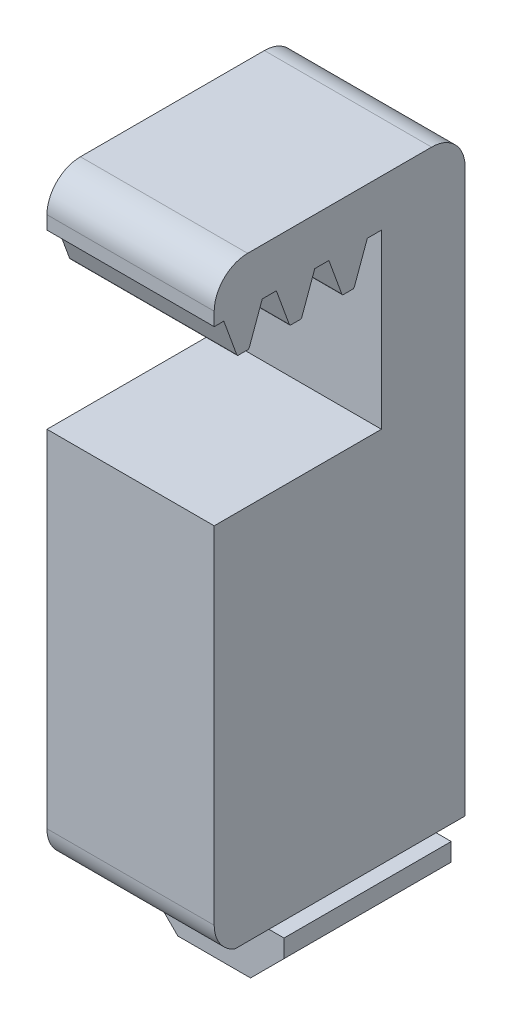
SolidWorks part; units mm, degrees
material "PLA Grey"
ref_plane "Front Plane" through (0, 0, 0) normal (0, 0, 1) x (1, 0, 0)
ref_plane "Top Plane" through (0, 0, 0) normal (0, 1, 0) x (1, 0, 0)
ref_plane "Right Plane" through (0, 0, 0) normal (1, 0, 0) x (0, 0, -1)
sketch "Sketch1" plane through (0, 0, 0) normal (1, 0, 0) x (0, 0, -1)
  line L0 (6.35, 0) -> (6.35, -6.096)
  line L1 (0, 45.466) -> (12.7, 45.466)
  line L2 (0, 45.466) -> (0, 39.116)
  line L3 (0, 39.116) -> (12.7, 39.116)
  line L5 (12.7, 45.466) -> (19.05, 45.466)
  line L6 (12.7, 39.116) -> (12.7, 29.21)
  line L7 (6.35, -6.096) -> (19.05, -6.096)
  line L8 (19.05, 45.466) -> (19.05, -6.096)
  line L9 (12.7, 29.21) -> (0, 29.21)
  line L11 (6.35, 0) -> (0, 0)
  line L12 (0, 29.21) -> (0, 0)
  line L13 (12.7, 29.21) -> (-1206.5, 29.21) construction
  dimension "D1" = 6.35
  dimension "D2" = 12.7
  dimension "D3" = 9.906
  dimension "D4" = 6.35
  dimension "D5" = 12.7
  dimension "D6" = 6.096
extrude "Boss-Extrude1" add sketch "Sketch1" along normal mid plane 12.7
sketch "Sketch2" plane through (6.35, 0, 0) normal (1, 0, 0) x (0, 0, -1)
  line L0 (3.6499, 41.91) -> (4.7203, 41.91) construction
  line L1 (5.6948, 39.2327) -> (4.7203, 41.91) construction
  line L2 (6.4261, 39.0652) -> (5.934, 39.0652) construction
  line L3 (7.6397, 41.91) -> (6.6653, 39.2327) construction
  line L4 (7.6397, 41.91) -> (8.7102, 41.91) construction
  line L5 (9.6846, 39.2327) -> (8.7102, 41.91) construction
  line L6 (10.4159, 39.0652) -> (9.9238, 39.0652) construction
  line L7 (11.6296, 41.91) -> (10.6551, 39.2327) construction
  line L8 (11.6296, 41.91) -> (12.7, 41.91) construction
  line L9 (3.6499, 41.91) -> (4.7203, 41.91)
  line L10 (5.6948, 39.2327) -> (4.7203, 41.91)
  line L11 (6.4261, 39.0652) -> (5.934, 39.0652)
  line L12 (7.6397, 41.91) -> (6.6653, 39.2327)
  line L13 (7.6397, 41.91) -> (8.7102, 41.91)
  line L14 (9.6846, 39.2327) -> (8.7102, 41.91)
  line L15 (10.4159, 39.0652) -> (9.9238, 39.0652)
  line L16 (11.6296, 41.91) -> (10.6551, 39.2327)
  line L17 (11.6296, 41.91) -> (12.7, 41.91)
  line L18 (12.7, 41.91) -> (12.7, 29.21)
  line L19 (12.7, 39.116) -> (12.7, 29.21) construction
  line L20 (12.7, 29.21) -> (3.6499, 29.21)
  line L21 (3.6499, 29.21) -> (3.6499, 41.91)
  line L22 (12.7, 29.21) -> (0, 29.21) construction
  arc A0 (5.6948, 39.2327) -> (5.934, 39.0652) centre (5.934, 39.3198) ccw construction
  arc A1 (6.4261, 39.0652) -> (6.6653, 39.2327) centre (6.4261, 39.3198) ccw construction
  arc A2 (9.6846, 39.2327) -> (9.9238, 39.0652) centre (9.9238, 39.3198) ccw construction
  arc A3 (10.4159, 39.0652) -> (10.6551, 39.2327) centre (10.4159, 39.3198) ccw construction
  arc A4 (5.6948, 39.2327) -> (5.934, 39.0652) centre (5.934, 39.3198) ccw
  arc A5 (6.4261, 39.0652) -> (6.6653, 39.2327) centre (6.4261, 39.3198) ccw
  arc A6 (9.6846, 39.2327) -> (9.9238, 39.0652) centre (9.9238, 39.3198) ccw
  arc A7 (10.4159, 39.0652) -> (10.6551, 39.2327) centre (10.4159, 39.3198) ccw
extrude "Cut-Extrude1" cut sketch "Sketch2" against normal through all
pattern_linear "LPattern1" count 10 spacing 3.9898 along (0, 0, 1) of "Cut-Extrude1"
sketch "Sketch3" plane through (0, 0, -19.05) normal (0, 0, -1) x (-1, 0, 0)
  line L0 (-6.35, -6.096) -> (-2.8393, -6.1)
  line L1 (2.8393, -6.1) -> (5.5, -3.4393) construction
  line L2 (5.5, -3.4393) -> (5.5, -1.8) construction
  line L3 (5.5, -1.8) -> (3.125, -1.8) construction
  line L4 (3.125, -1.8) -> (3.125, -1.455) construction
  line L5 (3.125, -1.455) -> (4.58, 0) construction
  line L6 (15.42, 0) -> (4.58, 0) construction
  line L7 (-4.58, 0) -> (-9.5, 0) construction
  line L8 (-3.125, -1.455) -> (-4.58, 0) construction
  line L9 (-3.125, -1.8) -> (-3.125, -1.455) construction
  line L10 (-5.5, -1.8) -> (-3.125, -1.8) construction
  line L11 (-5.5, -3.4393) -> (-5.5, -1.8) construction
  line L12 (-2.8393, -6.1) -> (-5.5, -3.4393) construction
  line L13 (2.8393, -6.1) -> (6.35, -6.096)
  line L15 (2.8393, -6.1) -> (5.5, -3.4393)
  line L16 (5.5, -3.4393) -> (5.5, -1.8)
  line L17 (5.5, -1.8) -> (3.125, -1.8)
  line L18 (3.125, -1.8) -> (3.125, -1.455)
  line L19 (3.125, -1.455) -> (4.58, 0)
  line L20 (15.42, 0) -> (4.58, 0)
  line L21 (-4.58, 0) -> (-9.5, 0)
  line L22 (-3.125, -1.455) -> (-4.58, 0)
  line L23 (-3.125, -1.8) -> (-3.125, -1.455)
  line L24 (-5.5, -1.8) -> (-3.125, -1.8)
  line L25 (-5.5, -3.4393) -> (-5.5, -1.8)
  line L26 (-2.8393, -6.1) -> (-5.5, -3.4393)
  line L29 (-9.5, 0) -> (-6.35, -6.096)
  line L32 (6.35, -6.096) -> (15.42, 0)
extrude "Cut-Extrude2" cut sketch "Sketch3" against normal through all
fillet "Fillet1" radius 2.54 3 edges at (0, 0, 0) (0, 45.466, 0) (0, 45.466, -19.05)
sketch "Sketch5" plane through (0, 0, -19.05) normal (0, 0, -1) x (-1, 0, 0)
  line L0 (6.35, 0) -> (4.58, 0) construction
  line L1 (4.58, 0) -> (3.125, -1.455) construction
  line L2 (3.125, -1.455) -> (3.125, -1.8) construction
  line L3 (3.125, -1.8) -> (5.5, -1.8) construction
  line L4 (5.5, -1.8) -> (5.5, -3.4393) construction
  line L5 (5.5, -3.4393) -> (2.8433, -6.096) construction
  line L6 (-2.8433, -6.096) -> (2.8433, -6.096) construction
  line L7 (-2.8433, -6.096) -> (-5.5, -3.4393) construction
  line L8 (-5.5, -3.4393) -> (-5.5, -1.8) construction
  line L9 (-5.5, -1.8) -> (-3.125, -1.8) construction
  line L10 (-3.125, -1.8) -> (-3.125, -1.455) construction
  line L11 (-3.125, -1.455) -> (-4.58, 0) construction
  line L12 (-4.58, 0) -> (-6.35, 0) construction
  line L13 (6.35, 0) -> (4.58, 0)
  line L14 (4.58, 0) -> (3.125, -1.455)
  line L15 (3.125, -1.455) -> (3.125, -1.8)
  line L16 (3.125, -1.8) -> (5.5, -1.8)
  line L17 (5.5, -1.8) -> (5.5, -3.4393)
  line L18 (5.5, -3.4393) -> (2.8433, -6.096)
  line L19 (-2.8433, -6.096) -> (2.8433, -6.096)
  line L20 (-2.8433, -6.096) -> (-5.5, -3.4393)
  line L21 (-5.5, -3.4393) -> (-5.5, -1.8)
  line L22 (-5.5, -1.8) -> (-3.125, -1.8)
  line L23 (-3.125, -1.8) -> (-3.125, -1.455)
  line L24 (-3.125, -1.455) -> (-4.58, 0)
  line L25 (-4.58, 0) -> (-6.35, 0)
  line L26 (6.35, 0.1984) -> (4.4978, 0.1984)
  line L27 (4.4978, 0.1984) -> (2.9266, -1.3728)
  line L28 (2.9266, -1.3728) -> (2.9266, -1.9984)
  line L29 (2.9266, -1.9984) -> (5.3016, -1.9984)
  line L30 (5.3016, -1.9984) -> (5.3016, -3.3571)
  line L31 (5.3016, -3.3571) -> (2.7611, -5.8976)
  line L32 (-2.7611, -5.8976) -> (2.7611, -5.8976)
  line L33 (-2.7611, -5.8976) -> (-5.3016, -3.3571)
  line L34 (-5.3016, -3.3571) -> (-5.3016, -1.9984)
  line L35 (-5.3016, -1.9984) -> (-2.9266, -1.9984)
  line L36 (-2.9266, -1.9984) -> (-2.9266, -1.3728)
  line L37 (-2.9266, -1.3728) -> (-4.4978, 0.1984)
  line L38 (-4.4978, 0.1984) -> (-6.35, 0.1984)
  line L39 (6.35, 0) -> (6.35, 0.1984)
  line L40 (-6.35, 0) -> (-6.35, 0.1984)
  dimension "D1" = 0.1984
extrude "Cut-Extrude3" cut sketch "Sketch5" against normal through all
sketch "Sketch6" plane through (6.35, 0, 0) normal (1, 0, 0) x (0, 0, -1)
  line L0 (12.7, 41.91) -> (12.7, 29.21) construction
  line L1 (0, 29.21) -> (12.7, 29.21)
  line L2 (0, 29.21) -> (0, 28.8131)
  line L3 (0, 28.8131) -> (12.7, 28.8131)
  line L4 (12.7, 29.21) -> (12.7, 28.8131)
  dimension "D1" = 0.3969
extrude "Cut-Extrude4" cut sketch "Sketch6" against normal through all
sketch "Sketch7" [suppressed] plane through (6.35, 0, 0) normal (1, 0, 0) x (0, 0, -1)
  line L0 (19.05, 0.1984) -> (19.05, 42.926) construction
  line L1 (0, 28.8131) -> (19.05, 28.8131)
  line L2 (0, 28.8131) -> (0, 45.466)
  line L3 (0, 45.466) -> (19.05, 45.466)
  line L4 (19.05, 28.8131) -> (19.05, 45.466)
  line L5 (0, 28.8131) -> (19.05, 45.466) construction
  line L6 (0, 45.466) -> (19.05, 28.8131) construction
  line L7 (16.51, 45.466) -> (2.54, 45.466) construction
  point P4 (9.525, 37.1396)
extrude "Cut-Extrude5" [suppressed] cut sketch "Sketch7" against normal through all and the other way through all
